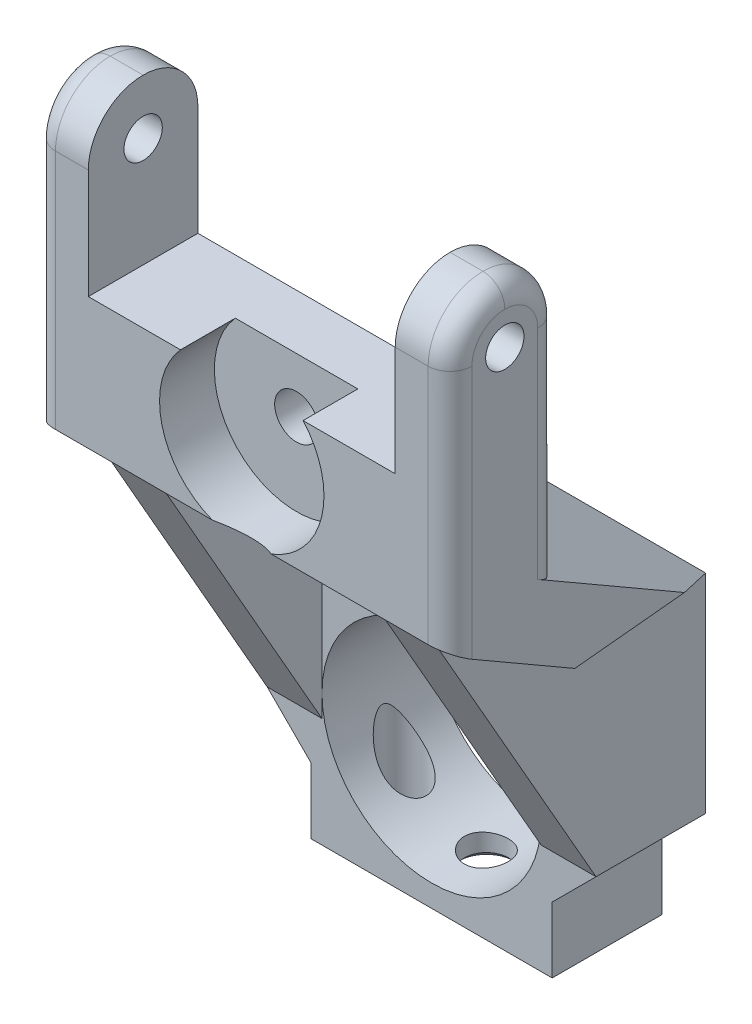
SolidWorks part; units mm, degrees
ref_plane "Front Plane" through (0, 0, 0) normal (0, 0, 1) x (1, 0, 0)
ref_plane "Top Plane" through (0, 0, 0) normal (0, 1, 0) x (1, 0, 0)
ref_plane "Right Plane" through (0, 0, 0) normal (1, 0, 0) x (0, 0, -1)
sketch "Sketch1" plane through (0, 0, 0) normal (0, 0, 1) x (1, 0, 0)
  line L1 (-15, -14.5) -> (15, -14.5)
  line L2 (-15, -14.5) -> (-15, 14.5)
  line L3 (-15, 14.5) -> (15, 14.5)
  line L4 (15, -14.5) -> (15, 14.5)
  line L5 (-15, -14.5) -> (15, 14.5) construction
  line L6 (-15, 14.5) -> (15, -14.5) construction
  point P0 (0, 0)
  dimension "D1" = 30
  dimension "3" = 29
extrude "Boss-Extrude1" add sketch "Sketch1" along normal blind 10
sketch "Sketch2" plane through (0, -14.5, 0) normal (0, -1, 0) x (1, 0, 0)
  line L0 (-15, 0) -> (15, 0) construction
  line L1 (-15, 10) -> (-11, 10)
  line L2 (-15, 10) -> (-15, 0)
  line L3 (-15, 0) -> (-11, 0)
  line L4 (-11, 10) -> (-11, 0)
  line L5 (-15, 10) -> (15, 10) construction
  line L6 (15, 0) -> (11, 0)
  line L7 (15, 0) -> (15, 10)
  line L8 (15, 10) -> (11, 10)
  line L9 (11, 0) -> (11, 10)
  dimension "D1" = 4
extrude "Cut-Extrude1" cut sketch "Sketch2" against normal blind 10
chamfer "Chamfer1" distance 4 angle 45 2 edges at (11, -4.5, 5) (-11, -4.5, 5)
sketch "Sketch3" plane through (0, -14.5, 0) normal (0, -1, 0) x (1, 0, 0)
  line L0 (-7.5, 5) -> (7.5, 5) construction
  line L1 (0, 5) -> (0, 0) construction
  circle A0 centre (-7.5, 5) radius 2
  circle A1 centre (0, 5) radius 2
  circle A2 centre (7.5, 5) radius 2
  dimension "D3" = 4
  dimension "D1" = 5
  dimension "D2" = 15
extrude "Cut-Extrude2" cut sketch "Sketch3" against normal blind 15
chamfer "Chamfer2" distance 0.5 angle 45 3 edges at (-7.5, -14.5, 3) (0, -14.5, 3) (7.5, -14.5, 3)
sketch "Sketch4" plane through (0, 0, 0) normal (0, 0, -1) x (-1, 0, 0)
  line L0 (0, 0) -> (0, -2.5) construction
  line L1 (11, -14.5) -> (-11, -14.5) construction
  circle A0 centre (0, -2.5) radius 10
  dimension "D1" = 20
  dimension "D2" = 12
extrude "Cut-Extrude3" cut sketch "Sketch4" against normal through all
sketch "Sketch5" plane through (0, 0, 0) normal (1, 0, 0) x (0, 0, -1)
  line L0 (-10, 13.5) -> (-27.3205, 23.5)
  line L1 (-27.3205, 23.5) -> (-27.3205, 50.5)
  line L2 (-27.3205, 50.5) -> (-17.3205, 50.5)
  line L3 (-17.3205, 50.5) -> (-17.3205, 24.5)
  line L4 (-17.3205, 24.5) -> (0, 14.5)
  line L5 (0, -4.5) -> (0, 14.5) construction
  line L8 (-10, -4.5) -> (-10, 14.5) construction
  line L9 (-10, 13.5) -> (0, 14.5)
  line L10 (-10, 14.5) -> (0, 14.5) construction
  dimension "D1" = 26
  dimension "D2" = 30
  dimension "D3" = 10
  dimension "D4" = 36
  dimension "D5" = 1
extrude "Boss-Extrude2" add sketch "Sketch5" along normal mid plane 38
chamfer "Chamfer3" distance 4 angle 45 2 edges at (-19, 14, 5) (19, 14, 5)
sketch "Sketch6" plane through (0, 50.5, 0) normal (0, 1, 0) x (1, 0, 0)
  line L0 (19, -17.3205) -> (-19, -17.3205) construction
  line L1 (-14, -17.3205) -> (14, -17.3205)
  line L2 (-14, -17.3205) -> (-14, -27.3205)
  line L3 (-14, -27.3205) -> (14, -27.3205)
  line L4 (14, -17.3205) -> (14, -27.3205)
  line L5 (19, -27.3205) -> (-19, -27.3205) construction
  line L6 (0, -17.3205) -> (0, 0) construction
  line L7 (-19, -17.3205) -> (-19, -27.3205) construction
  dimension "D1" = 5
extrude "Cut-Extrude4" cut sketch "Sketch6" against normal blind 15
fillet "Fillet1" radius 5 4 edges at (16.5, 50.5, 17.3205) (16.5, 50.5, 27.3205) (-16.5, 50.5, 17.3205) (-16.5, 50.5, 27.3205)
sketch "Sketch7" plane through (19, 0, 0) normal (1, 0, 0) x (0, 0, -1)
  circle A0 centre (-22.3205, 45.5) radius 1.75
  dimension "D1" = 3.5
extrude "Cut-Extrude5" cut sketch "Sketch7" against normal through all
fillet "Fillet2" radius 2 8 edges at (-19, 34.5, 27.3205) (-19, 49.0355, 25.856) (-19, 49.0355, 18.785) (19, 34.5, 27.3205) (19, 49.0355, 25.856) (19, 49.0355, 18.785) (-19, 35, 17.3205) (19, 35, 17.3205)
sketch "Sketch8" plane through (0, 0, 27.3205) normal (0, 0, 1) x (1, 0, 0)
  line L0 (0, 30.5) -> (0, 35.5) construction
  line L1 (-14, 35.5) -> (14, 35.5) construction
  circle A0 centre (0, 30.5) radius 2
  dimension "D2" = 4
  dimension "D1" = 5
extrude "Cut-Extrude6" cut sketch "Sketch8" against normal through all
sketch "Sketch9" plane through (0, 0, 27.3205) normal (0, 0, 1) x (1, 0, 0)
  circle A0 centre (0, 30.5) radius 7.5
  dimension "D1" = 15
extrude "Cut-Extrude7" cut sketch "Sketch9" against normal blind 5
sketch "Sketch10" plane through (15, 0, 0) normal (1, 0, 0) x (0, 0, -1)
  line L0 (-10, -4.5) -> (-25.3205, 22.3453)
  line L1 (-25.3205, 22.3453) -> (-15.9348, 16.9265) construction
  line L2 (-25.3205, 22.3453) -> (-10, 13.5)
  line L3 (-10, 13.5) -> (-10, -4.5)
extrude "Boss-Extrude3" add sketch "Sketch10" against normal blind 5
mirror "Mirror1" about plane through (0, 0, 0) normal (1, 0, 0) of "Boss-Extrude3"
